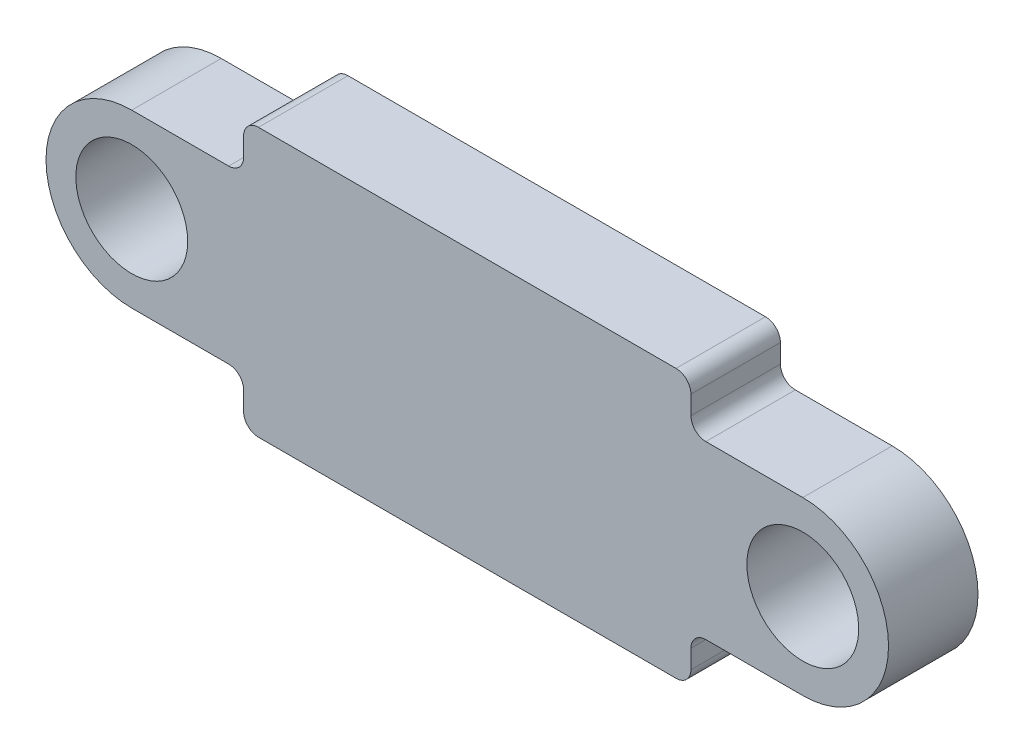
SolidWorks part; units mm, degrees
ref_plane "Front Plane" through (0, 0, 0) normal (0, 0, 1) x (1, 0, 0)
ref_plane "Top Plane" through (0, 0, 0) normal (0, 1, 0) x (1, 0, 0)
ref_plane "Right Plane" through (0, 0, 0) normal (1, 0, 0) x (0, 0, -1)
sketch "Sketch1" plane through (0, 0, 0) normal (0, 0, 1) x (1, 0, 0)
  line L0 (-45, 0) -> (45, 0) construction
  line L1 (0, 0) -> (0, 17.3262) construction
  line L2 (-45, 11.5) -> (-32, 11.5)
  line L3 (-30, 13.5) -> (-30, 16)
  line L4 (-28, 18) -> (28, 18)
  line L5 (-28, -18) -> (28, -18)
  line L6 (-30, -13.5) -> (-30, -16)
  line L7 (-45, -11.5) -> (-32, -11.5)
  line L8 (30, -13.5) -> (30, -16)
  line L9 (45, -11.5) -> (32, -11.5)
  line L10 (45, 11.5) -> (32, 11.5)
  line L11 (30, 13.5) -> (30, 16)
  circle A0 centre (-45, 0) radius 7.5
  arc A1 (-45, 11.5) -> (-45, -11.5) centre (-45, 0) ccw
  arc A2 (-32, 11.5) -> (-30, 13.5) centre (-32, 13.5) ccw
  arc A3 (-30, 16) -> (-28, 18) centre (-28, 16) cw
  arc A4 (-30, -16) -> (-28, -18) centre (-28, -16) ccw
  arc A5 (-32, -11.5) -> (-30, -13.5) centre (-32, -13.5) cw
  arc A6 (30, -16) -> (28, -18) centre (28, -16) cw
  arc A7 (32, -11.5) -> (30, -13.5) centre (32, -13.5) ccw
  arc A8 (45, 11.5) -> (45, -11.5) centre (45, 0) cw
  arc A9 (32, 11.5) -> (30, 13.5) centre (32, 13.5) cw
  arc A10 (30, 16) -> (28, 18) centre (28, 16) ccw
  circle A11 centre (45, 0) radius 7.5
  point P15 (0, 0)
  point P17 (-58.919, 0)
  point P18 (-30.5768, 14.1461)
  point P19 (-48.0008, 10.0494)
  point P20 (-58.0741, -0.0239)
  point P21 (-56.5481, 0)
  point P22 (-33.9821, 11.5)
  point P23 (-36.4781, 11.5)
  point P32 (0, -18)
  point P45 (0, 18)
  dimension "D2" = 15
  dimension "D3" = 4
  dimension "D6" = 2
  dimension "D1" = 90
  dimension "D4" = 36
  dimension "D5" = 30
extrude "Boss-Extrude1" add sketch "Sketch1" along normal blind 12
